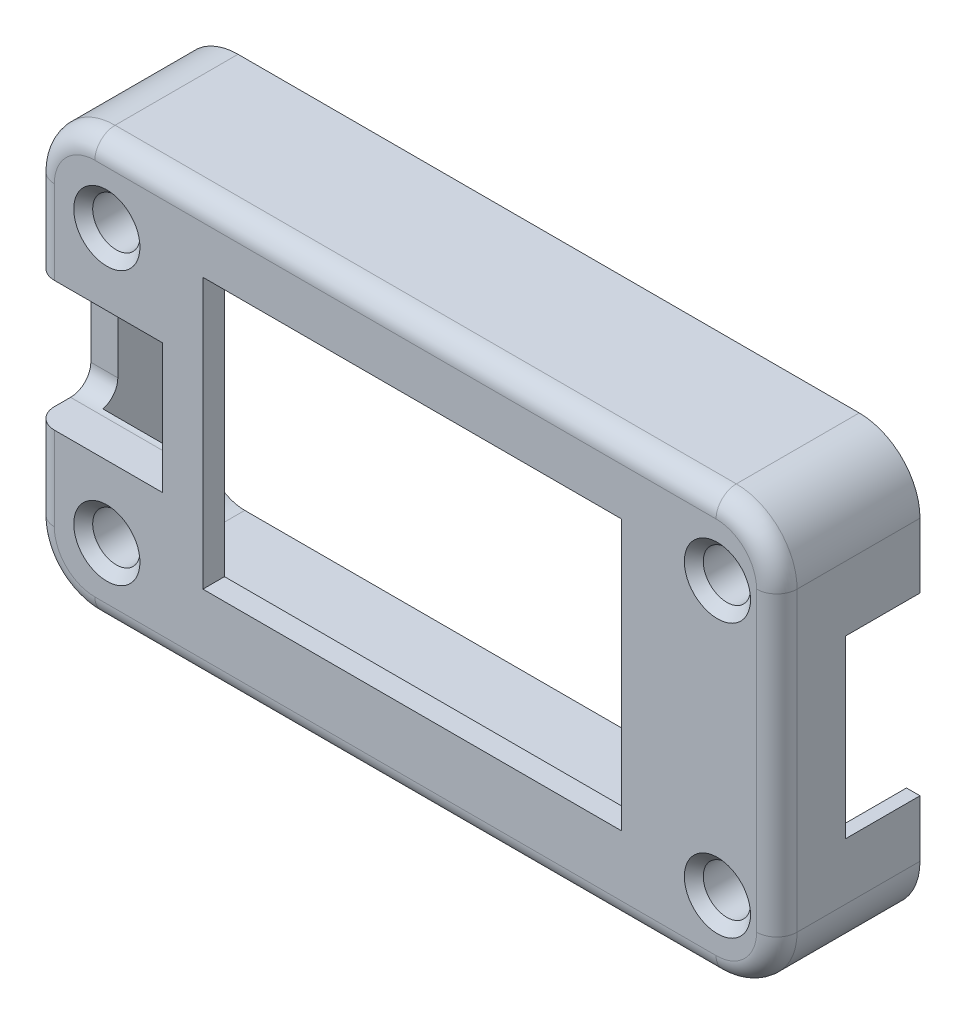
SolidWorks part; units mm, degrees
ref_plane "前视基准面" through (0, 0, 0) normal (0, 0, 1) x (1, 0, 0)
ref_plane "上视基准面" through (0, 0, 0) normal (0, 1, 0) x (1, 0, 0)
ref_plane "右视基准面" through (0, 0, 0) normal (1, 0, 0) x (0, 0, -1)
sketch "草图1" plane through (0, 0, 0) normal (0, 0, 1) x (1, 0, 0)
  line L0 (0, 0) -> (55, 0)
  line L1 (55, 0) -> (55, -31)
  line L2 (55, -31) -> (0, -31)
  line L3 (0, -31) -> (0, 0)
  line L4 (2, -2) -> (54, -2)
  line L5 (54, -2) -> (54, -29)
  line L6 (54, -29) -> (2, -29)
  line L7 (2, -29) -> (2, -2)
  dimension "D1" = 52
  dimension "D2" = 27
  dimension "D3" = 1
  dimension "D4" = 2
  dimension "D5" = 2
  dimension "D6" = 2
extrude "凸台-拉伸1" add sketch "草图1" along normal blind 9
sketch "草图2" plane through (0, 0, 9) normal (0, 0, 1) x (1, 0, 0)
  line L0 (55, -31) -> (55, 0) construction
  line L1 (0, -31) -> (55, -31) construction
  line L2 (0, 0) -> (0, -31) construction
  line L3 (55, 0) -> (0, 0) construction
  line L4 (55, -31) -> (55, 0)
  line L5 (0, -31) -> (55, -31)
  line L6 (0, 0) -> (0, -31)
  line L7 (55, 0) -> (0, 0)
extrude "凸台-拉伸2" add sketch "草图2" along normal blind 1.6
sketch "草图3" plane through (0, 0, 10.6) normal (0, 0, 1) x (1, 0, 0)
  line L0 (12.5, -5) -> (43.5, -5)
  line L1 (43.5, -5) -> (43.5, -25)
  line L2 (43.5, -25) -> (12.5, -25)
  line L3 (12.5, -25) -> (12.5, -5)
  line L4 (0, 0) -> (0, -31) construction
  line L8 (0, -31) -> (55, -31) construction
  dimension "D1" = 31
  dimension "D2" = 20
  dimension "D3" = 12.5
  dimension "D4" = 6
extrude "切除-拉伸1" cut sketch "草图3" against normal up to next
sketch "草图4" plane through (0, 0, 9) normal (0, 0, -1) x (-1, 0, 0)
  line L0 (-45.5, -3) -> (-10.5, -3)
  line L1 (-10.5, -3) -> (-10.5, -27)
  line L2 (-10.5, -27) -> (-45.5, -27)
  line L3 (-45.5, -27) -> (-45.5, -3)
  line L4 (-2, -29) -> (-54, -29) construction
  line L5 (-54, -29) -> (-54, -2) construction
  line L6 (-54, -2) -> (-2, -2) construction
  line L7 (-2, -2) -> (-2, -29) construction
  line L8 (-2, -29) -> (-54, -29)
  line L9 (-54, -29) -> (-54, -2)
  line L10 (-54, -2) -> (-2, -2)
  line L11 (-2, -2) -> (-2, -29)
  line L13 (-12.5, -25) -> (-12.5, -5) construction
  line L14 (-43.5, -5) -> (-43.5, -25) construction
  dimension "D1" = 1
  dimension "D2" = 2
  dimension "D3" = 2
  dimension "D4" = 2
extrude "凸台-拉伸3" add sketch "草图4" along normal blind 1.5
sketch "草图5" plane through (0, 0, 7.5) normal (0, 0, -1) x (-1, 0, 0)
  line L0 (-35.5, -27) -> (-20.5, -27)
  line L1 (-45.5, -27) -> (-10.5, -27) construction
  line L2 (-20.5, -27) -> (-20.5, -29)
  line L3 (-2, -29) -> (-54, -29) construction
  line L4 (-20.5, -29) -> (-35.5, -29)
  line L5 (-35.5, -29) -> (-35.5, -27)
  line L6 (-45.5, -3) -> (-45.5, -27) construction
  line L7 (-10.5, -27) -> (-10.5, -3) construction
  dimension "D1" = 10
  dimension "D2" = 10
extrude "切除-拉伸2" cut sketch "草图5" against normal blind 1.5
sketch "草图7" plane through (0, 0, 10.6) normal (0, 0, 1) x (1, 0, 0)
  line L0 (0, -10.7) -> (9.5, -10.7)
  line L1 (0, 0) -> (0, -31) construction
  line L2 (9.5, -10.7) -> (9.5, -20.3)
  line L3 (9.5, -20.3) -> (0, -20.3)
  line L4 (0, -20.3) -> (0, -10.7)
  line L5 (55, 0) -> (0, 0) construction
  dimension "D1" = 9.6
  dimension "D2" = 10.7
  dimension "D3" = 9.5
extrude "切除-拉伸4" cut sketch "草图7" against normal blind 4.2
sketch "草图8" plane through (0, 0, 7.5) normal (0, 0, -1) x (-1, 0, 0)
  line L0 (-9.5, -10.7) -> (-10.5, -10.7)
  line L1 (-10.5, -27) -> (-10.5, -3) construction
  line L2 (-10.5, -10.7) -> (-10.5, -20.3)
  line L3 (-10.5, -27) -> (-10.5, -3) construction
  line L4 (-10.5, -20.3) -> (-9.5, -20.3)
  line L5 (-9.5, -20.3) -> (-9.5, -10.7)
extrude "切除-拉伸5" cut sketch "草图8" against normal blind 1.5
sketch "草图9" plane through (0, 0, 0) normal (0, 0, -1) x (-1, 0, 0)
  line L0 (-55, -9.3) -> (-54, -9.3)
  line L1 (-55, -31) -> (-55, 0) construction
  line L2 (-54, -29) -> (-54, -2) construction
  line L3 (-54, -9.3) -> (-54, -22.3)
  line L4 (-54, -22.3) -> (-55, -22.3)
  line L5 (-55, -22.3) -> (-55, -9.3)
  line L6 (-54, -2) -> (-2, -2) construction
  dimension "D1" = 13
  dimension "D2" = 7.3
extrude "切除-拉伸6" cut sketch "草图9" against normal blind 5.5
sketch "草图10" plane through (0, 0, 7.5) normal (0, 0, -1) x (-1, 0, 0)
  line L0 (-54, -2) -> (-54, -29) construction
  line L2 (-54, -2) -> (-2, -2) construction
  circle A0 centre (-50.6, -5.4) radius 1.75
  circle A1 centre (-5.388, -5.4) radius 1.75
  circle A2 centre (-5.388, -25.6) radius 1.75
  circle A3 centre (-50.6, -25.6) radius 1.75
  dimension "D1" = 45.212
  dimension "D3" = 3.5
  dimension "D2" = 20.2
  dimension "D4" = 3.4
  dimension "D5" = 3.4
extrude "切除-拉伸7" cut sketch "草图10" against normal through all
fillet "圆角1" radius 3 4 edges at (2, -29, 3.75) (54, -29, 3.75) (54, -2, 3.75) (2, -2, 3.75)
fillet "圆角2" radius 4.5 4 edges at (0, 0, 5.3) (0, -31, 5.3) (55, -31, 5.3) (55, 0, 5.3)
fillet "圆角3" radius 1.5 2 edges at (1, -20.3, 6.4) (1, -10.7, 6.4)
fillet "圆角4" radius 1.5 9 edges at (0, -23.4, 10.6) (1.318, -29.682, 10.6) (0, -7.6, 10.6) (1.318, -1.318, 10.6) (27.5, 0, 10.6) (53.682, -1.318, 10.6) (55, -15.5, 10.6) (53.682, -29.682, 10.6) (27.5, -31, 10.6)
chamfer "倒角1" distance 0.7 angle 45 4 edges at (3.638, -5.4, 10.6) (3.638, -25.6, 10.6) (48.85, -5.4, 10.6) (48.85, -25.6, 10.6)
